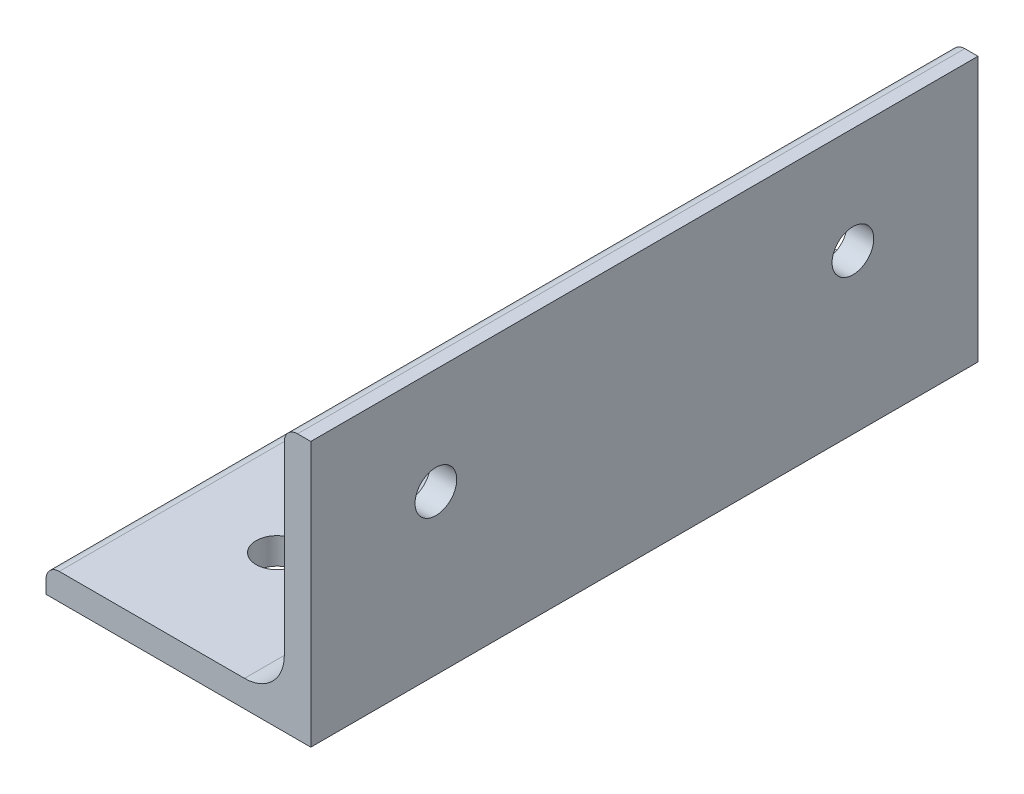
SolidWorks part; units mm, degrees
ref_plane "Front Plane" through (0, 0, 0) normal (0, 0, 1) x (1, 0, 0)
ref_plane "Top Plane" through (0, 0, 0) normal (0, 1, 0) x (1, 0, 0)
ref_plane "Right Plane" through (0, 0, 0) normal (1, 0, 0) x (0, 0, -1)
sketch "Sketch0" plane through (0, 0, 0) normal (0, 0, 1) x (1, 0, 0)
  line L0 (-15.875, -15.875) -> (15.875, -15.875)
  line L1 (15.875, -15.875) -> (15.875, 15.875)
  line L2 (15.875, 0) -> (0, 0) construction
  line L3 (0, 0) -> (0, -15.875) construction
  line L4 (12.7, -7.9248) -> (12.7, 15.875) construction
  line L5 (7.9248, -12.7) -> (-15.875, -12.7) construction
  arc A0 (12.7, -7.9248) -> (7.9248, -12.7) centre (7.9248, -7.9248) cw
  point P3 (11.3014, -11.3014)
  dimension "Inside Corner Radius" = 4.7752
  dimension "Outside Height" = 31.75
  dimension "Inside Height" = 28.575
  dimension "Inside Width" = 28.575
  dimension "Wall Thickness" = 3.175
  dimension "D1" = 3.175
  dimension "Outside Width" = 31.75
sketch "Sketch1" plane through (0, 0, 0) normal (1, 0, 0) x (0, 0, -1)
  line L0 (304.8, 0) -> (-304.8, 0)
  point P4 (0, 0)
  dimension "Length" = 609.6
sketch "Sketch2" plane through (0, 0, 0) normal (0, 0, 1) x (1, 0, 0)
  line L0 (-15.875, -15.875) -> (15.875, -15.875)
  line L1 (15.875, -15.875) -> (15.875, 15.875)
  line L2 (15.875, 15.875) -> (12.7, 15.875) construction
  line L3 (12.7, 14.2875) -> (12.7, -7.9248)
  line L4 (7.9248, -12.7) -> (-14.2875, -12.7)
  line L5 (-15.875, -15.875) -> (-15.875, -12.7) construction
  line L6 (14.2875, 15.875) -> (15.875, 15.875)
  line L7 (-15.875, -14.2875) -> (-15.875, -15.875)
  line L8 (15.875, 0) -> (0, 0) construction
  line L9 (0, 0) -> (0, -15.875) construction
  arc A0 (12.7, 14.2875) -> (14.2875, 15.875) centre (14.2875, 14.2875) cw
  arc A1 (-15.875, -14.2875) -> (-14.2875, -12.7) centre (-14.2875, -14.2875) cw
  arc A2 (12.7, -7.9248) -> (7.9248, -12.7) centre (7.9248, -7.9248) cw
  dimension "Inside Radius" = 4.7752
  dimension "Height" = 31.75
  dimension "Width" = 31.75
  dimension "Thickness" = 3.175
extrude "Boss-Extrude1" add sketch "Sketch2" along normal mid plane 609.6
sketch "Break Locations" plane through (0, 0, 0) normal (1, 0, 0) x (0, 0, -1)
  line L0 (-272.415, 0) -> (272.415, 0)
  line L1 (-304.8, -15.875) -> (-304.8, 15.875) construction
  line L2 (304.8, -15.875) -> (304.8, 15.875) construction
  point P0 (-277.8125, 0)
  point P1 (277.8125, 0)
  point P10 (0, 0)
  point P11 (272.415, 0)
  point P13 (-272.415, 0)
  dimension "D1" = 26.9875
  dimension "D2" = 26.9875
  dimension "D3" = 32.385
sketch "Sketch3" plane through (0, 0, -304.8) normal (0, 0, -1) x (-1, 0, 0)
  line L1 (-15.875, -15.875) -> (18.5395, -15.875)
  line L2 (-15.875, -15.875) -> (-15.875, 17.7829)
  line L3 (-15.875, 17.7829) -> (18.5395, 17.7829)
  line L4 (18.5395, -15.875) -> (18.5395, 17.7829)
extrude "Cut-Extrude1" cut sketch "Sketch3" against normal offset from surface (529.6 mm away) 80 up to face at (3.7396, -3.7396, 304.8)
sketch "Sketch4" plane through (0, -12.7, 0) normal (0, 1, 0) x (1, 0, 0)
  line L0 (-14.2875, -224.8) -> (7.9248, -224.8) construction
  line L1 (7.9248, -304.8) -> (-14.2875, -304.8) construction
  circle A0 centre (-3.1813, -239.8) radius 2.5
  circle A1 centre (-3.1813, -289.8) radius 2.5
  point P5 (-3.1813, -224.8)
  dimension "D1" = 5
  dimension "D2" = 5
  dimension "D3" = 15
  dimension "D4" = 15
sketch "Sketch5" plane through (12.7, 0, 0) normal (-1, 0, 0) x (0, 0, 1)
  line L0 (224.8, -7.9248) -> (224.8, 14.2875) construction
  line L1 (304.8, 14.2875) -> (304.8, -7.9248) construction
  circle A2 centre (289.8, 3.1813) radius 2.5
  circle A3 centre (239.8, 3.1813) radius 2.5
  point P3 (224.8, 3.1813)
  dimension "D1" = 5
  dimension "D2" = 5
  dimension "D3" = 15
  dimension "D4" = 15
extrude "Cut-Extrude2" cut sketch "Sketch5" against normal blind 101.6
extrude "Cut-Extrude3" cut sketch "Sketch4" against normal blind 101.6
equation "\"D1@Break Locations\" = .85 * \"Height@Sketch2\""
equation "\"D2@Break Locations\"=\"D1@Break Locations\""
equation "\"Thickness@Sketch2\"=\"wall thickness@sketch0\""
equation "\"Height@Sketch2\"=\"outside height@sketch0\""
equation "\"Width@Sketch2\"=\"outside width@sketch0\""
equation "\"Inside Radius@Sketch2\"=\"inside corner radius@sketch0\""
equation "\"Length@Boss-Extrude1\"=\"length@sketch1\""
equation "\"D3@Break Locations\"=\"D2@Break Locations\"*1.2"
equation "\"D1@Sketch0\"=\"Wall Thickness@Sketch0\""
equation "\"D2@Sketch4\"=\"D1@Sketch4\""
